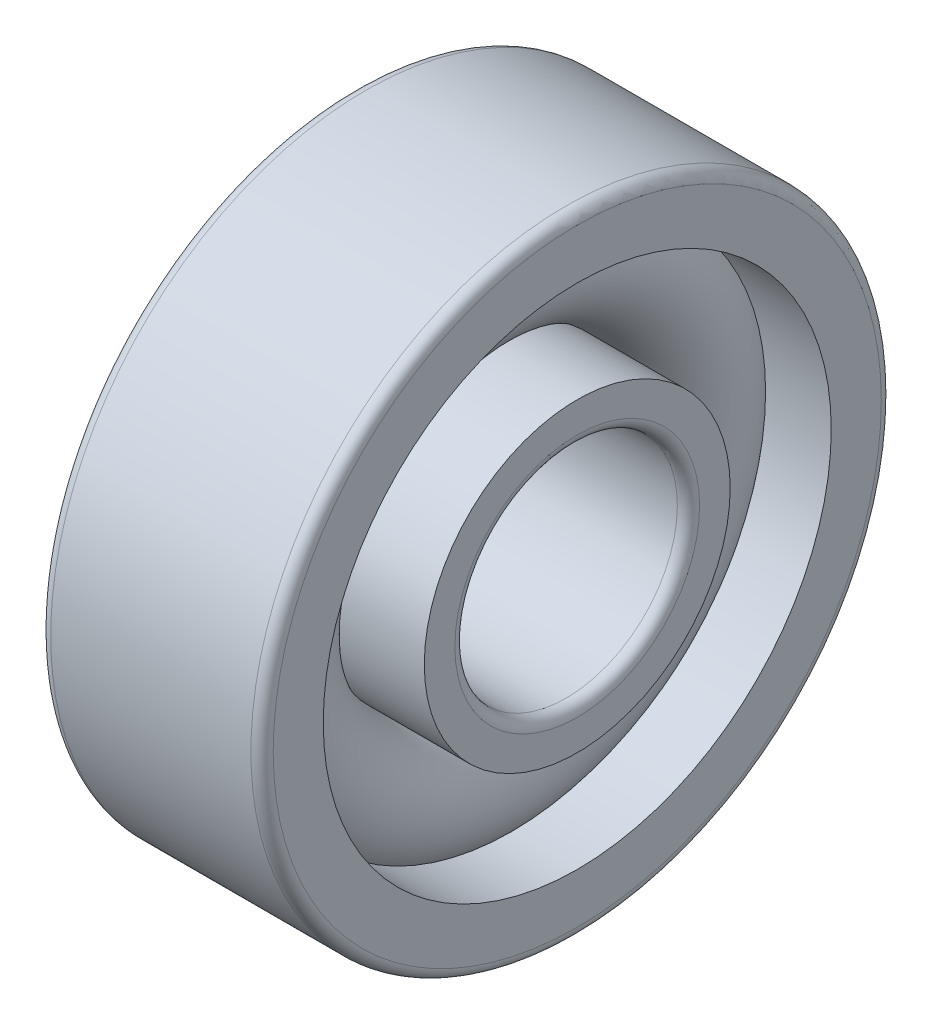
SolidWorks part; units mm, degrees
ref_plane "Plane1" through (0, 0, 0) normal (0, 0, 1) x (1, 0, 0)
ref_plane "Plane2" through (0, 0, 0) normal (0, 1, 0) x (1, 0, 0)
ref_plane "Plane3" through (0, 0, 0) normal (1, 0, 0) x (0, 0, -1)
sketch "Clipboard" plane through (0, 0, 0) normal (0, 0, 1) x (1, 0, 0)
  line L0 (-10, 0) -> (10, 0) construction
  line L1 (0, 0) -> (22.3471, -0.7804)
  line L2 (0, 0) -> (5.7465, 0.2007)
  line L3 (0, 0) -> (22.3471, -0.7804)
  line L4 (0, 0) -> (-22.3573, -0.3902)
  dimension "BallCLRad" = 5.75
sketch "CagSpiSke" plane through (0, 0, 0) normal (0, 0, 1) x (1, 0, 0)
  line L0 (0.4125, 5.475) -> (0.4125, 6.025)
  line L1 (0.4125, 6.025) -> (-0.4125, 6.025)
  line L2 (-0.4125, 6.025) -> (-0.4125, 5.475)
  line L3 (-0.4125, 5.475) -> (0.4125, 5.475)
  line L4 (-20.6375, 0) -> (20.6375, 0) construction
  line L5 (0, 0) -> (0, 23.7692) construction
  dimension "OD" = 12.05
  dimension "ID" = 10.95
revolve "CageSpine" add sketch "CagSpiSke" angle 0.001 about L4
ref_axis "Axis1" through (-50, 0, 0) along (1, 0, 0)
sketch "CagBalSke" plane through (0, 0, 0) normal (0, 0, 1) x (1, 0, 0)
  line L0 (-1.815, 5.75) -> (1.815, 5.75)
  line L1 (-1.905, 5.75) -> (1.905, 5.75) construction
  line L2 (-10, 0) -> (10, 0) construction
  line L3 (0, 0) -> (0, 24) construction
  arc A0 (1.815, 5.75) -> (-1.815, 5.75) centre (0, 5.75) cw
  dimension "BallCLRad" = 5.75
revolve "CageBall" [suppressed] add sketch "CagBalSke" angle 360 about L1 reverse direction yes
pattern_circular "CageBalls" [suppressed] count 2 every 180 about axis through (-50, 0, 0) along (1, 0, 0)
sketch "CagTrmODSke" plane through (0, 0, 0) normal (0, 0, 1) x (1, 0, 0)
  line L0 (1.816, 6.025) -> (1.816, 7.566)
  line L1 (1.816, 7.566) -> (-1.816, 7.566)
  line L2 (-1.816, 7.566) -> (-1.816, 6.025)
  line L3 (-1.816, 6.025) -> (1.816, 6.025)
  line L4 (-20.6375, 0) -> (20.6375, 0) construction
  line L5 (0, 0) -> (0, 25) construction
  dimension "Width" = 3.632
  dimension "ID" = 12.05
  dimension "OD" = 15.132
revolve "CageTrimOD" [suppressed] cut sketch "CagTrmODSke" angle 360 about L4 reverse direction yes
sketch "CagTrmIDSke" plane through (0, 0, 0) normal (0, 0, 1) x (1, 0, 0)
  line L0 (1.816, 3.936) -> (1.816, 5.475)
  line L1 (1.816, 5.475) -> (-1.816, 5.475)
  line L2 (-1.816, 5.475) -> (-1.816, 3.936)
  line L3 (-1.816, 3.936) -> (1.816, 3.936)
  line L4 (-20.6375, 0) -> (20.6375, 0) construction
  line L5 (0, 0) -> (0, 25) construction
  dimension "Width" = 3.632
  dimension "ID" = 7.872
  dimension "OD" = 10.95
revolve "CageTrimID" [suppressed] cut sketch "CagTrmIDSke" angle 360 about L4 reverse direction yes
sketch "BalSimSke" plane through (0, 0, 0) normal (0, 0, 1) x (1, 0, 0)
  line L0 (-10, 0) -> (10, 0) construction
  line L1 (-10, 5.75) -> (10, 5.75) construction
  line L2 (0, 0) -> (0, 23) construction
  circle A0 centre (0, 5.75) radius 1.65
  dimension "BallCLRad" = 5.75
  dimension "Ball_diameter" = 3.3
revolve "BallsSimplified" add sketch "BalSimSke" angle 360 about L0
sketch "BalDetSke" plane through (0, 0, 0) normal (0, 0, 1) x (1, 0, 0)
  line L0 (-1.65, 5.75) -> (1.65, 5.75)
  line L1 (-1.905, 5.75) -> (1.905, 5.75) construction
  line L2 (0, 0) -> (0, 25) construction
  arc A0 (1.65, 5.75) -> (-1.65, 5.75) centre (0, 5.75) cw
  dimension "BallCLRad" = 5.75
  dimension "Ball_diameter" = 3.3
revolve "BallDetailed" [suppressed] add sketch "BalDetSke" angle 360 about L1 reverse direction yes
sketch "InnRacSke" plane through (0, 0, 0) normal (0, 0, 1) x (1, 0, 0)
  line L0 (-1.1961, 4.65) -> (-3, 4.65)
  line L1 (-3, 4.65) -> (-3, 3.3)
  line L2 (-2.7, 3) -> (2.7, 3)
  line L3 (3, 3.3) -> (3, 4.125)
  line L4 (0, 4.125) -> (3, 4.125)
  line L5 (-20.6375, 0) -> (20.6375, 0) construction
  line L6 (0, 0) -> (0, 30) construction
  arc A0 (-3, 3.3) -> (-2.7, 3) centre (-2.7, 3.3) ccw
  arc A1 (2.7, 3) -> (3, 3.3) centre (2.7, 3.3) ccw
  arc A2 (0, 4.125) -> (-1.1961, 4.65) centre (0, 5.75) cw
  dimension "BallCLRad" = 5.75
  dimension "Fillet_radius" = 0.3
  dimension "Ball_diameter" = 3.25
  dimension "ID" = 6
  dimension "OD" = 9.3
  dimension "Width" = 6
revolve "InnerRace" add sketch "InnRacSke" angle 360 about L5 reverse direction yes
sketch "OutRacSke" plane through (0, 0, 0) normal (0, 0, 1) x (1, 0, 0)
  line L0 (0, 7.375) -> (-3, 7.375)
  line L1 (-3, 7.375) -> (-3, 8.2)
  line L2 (-2.7, 8.5) -> (2.7, 8.5)
  line L3 (3, 8.2) -> (3, 6.85)
  line L4 (3, 6.85) -> (1.1961, 6.85)
  line L5 (-20.6375, 0) -> (20.6375, 0) construction
  line L6 (0, 0) -> (0, 30) construction
  arc A0 (-3, 8.2) -> (-2.7, 8.5) centre (-2.7, 8.2) cw
  arc A1 (2.7, 8.5) -> (3, 8.2) centre (2.7, 8.2) cw
  arc A2 (1.1961, 6.85) -> (0, 7.375) centre (0, 5.75) ccw
  dimension "BallCLRad" = 5.75
  dimension "Fillet_radius" = 0.3
  dimension "Ball_diameter" = 3.25
  dimension "Width" = 6
revolve "OuterRace" add sketch "OutRacSke" angle 360 about L5 reverse direction yes
pattern_circular "BallsDetailed" [suppressed] count 2 every 180 about axis through (-50, 0, 0) along (1, 0, 0)
equation "\"BallCLRad@Clipboard\" = ( \"OD@OutRacSke\" + \"ID@InnRacSke\" ) / 4"
equation "\"BallCLRad@BalSimSke\" = \"BallCLRad@Clipboard\""
equation "\"BallCLRad@BalDetSke\" = \"BallCLRad@Clipboard\""
equation "\"BallCLRad@InnRacSke\" = \"BallCLRad@Clipboard\""
equation "\"BallCLRad@OutRacSke\" = \"BallCLRad@Clipboard\""
equation "\"Ball_diameter@InnRacSke\" = \"Ball_diameter@BalDetSke\" - 0.05"
equation "\"Ball_diameter@OutRacSke\" = \"Ball_diameter@BalDetSke\" - 0.05"
equation "\"Ball_diameter@BalSimSke\" = \"Ball_diameter@BalDetSke\""
equation "\"Width@OutRacSke\" = \"Width@InnRacSke\""
equation "\"Fillet_radius@OutRacSke\" = \"Fillet_radius@InnRacSke\""
equation "\"Max_count@Clipboard\" = int( 3.14159265 / atn(( \"Ball_diameter@BalDetSke\" / 2) / sqr( \"BallCLRad@Clipboard\"  *  \"BallCLRad@Clipboard\" - ( \"Ball_diameter@BalDetSke\" / 2) *  ( \"Ball_diameter@BalDetSke\" / 2))))"
equation "\"Max_count@Clipboard\" = ((sgn( \"Max_count@Clipboard\" - \"Count@Clipboard\" )-1)*( \"Max_count@Clipboard\" - \"Count@Clipboard\" ))/-2+ \"Count@Clipboard\""
equation "\"Count@BallsDetailed\" = int( \"Show_count@Clipboard\" ) "
equation "\"Count@BallsDetailed\" = ((sgn( \"Count@BallsDetailed\" - \"Max_count@Clipboard\" )-1)*( \"Count@BallsDetailed\" - \"Max_count@Clipboard\" ))/-2+ \"Max_count@Clipboard\""
equation "\"Count@BallsDetailed\" = ((sgn( \"Count@BallsDetailed\" - \"Min_count@Clipboard\" )+1)*( \"Count@BallsDetailed\" - \"Min_count@Clipboard\"))/2 +\"Min_count@Clipboard\""
equation "\"Angle@BallsDetailed\" = 360.0 / \"Max_count@Clipboard\""
equation "\"BallCLRad@CagBalSke\" = \"BallCLRad@Clipboard\""
equation "\"Count@CageBalls\" = \"Count@BallsDetailed\""
equation "\"Angle@CageBalls\" = \"Angle@BallsDetailed\""
equation "\"Angle@CageSpine\" =  \"Angle@CageBalls\" * ( \"Count@CageBalls\" -1 + int( \"Count@CageBalls\" / \"Max_count@Clipboard\" ) )  + 0.001 -  int( \"Count@CageBalls\" / \"Max_count@Clipboard\" ) * 0.001"
equation "\"Angle@CageSpine\" =  \"Angle@CageSpine\" * int( \"Min_count@Clipboard\" / 2) + int(1 / \"Min_count@Clipboard\")  * 0.001"
equation "\"CageWallOD@CagBalSke\" =  \"Ball_diameter@BalDetSke\" * 1.1"
equation "\"Thickness@CagSpiSke\" =  \"Ball_diameter@BalDetSke\" * 0.25"
equation "\"OD@CagTrmODSke\" = \"BallCLRad@Clipboard\" * 2 + \"CageWallOD@CagBalSke\" + 0.002"
equation "\"ID@CagTrmODSke\" = \"BallCLRad@Clipboard\" * 2 + \"Ball_diameter@BalDetSke\" / 6"
equation "\"OD@CagTrmIDSke\" = \"BallCLRad@Clipboard\" * 2 - \"Ball_diameter@BalDetSke\" / 6"
equation "\"ID@CagTrmIDSke\" = \"BallCLRad@Clipboard\" * 2 - \"CageWallOD@CagBalSke\" + 0.002"
equation "\"OD@CagSpiSke\" = \"ID@CagTrmODSke\""
equation "\"ID@CagSpiSke\" = \"OD@CagTrmIDSke\""
equation "\"Width@CagTrmODSke\" = \"CageWallOD@CagBalSke\" + 0.002"
equation "\"Width@CagTrmIDSke\" = \"CageWallOD@CagBalSke\" + 0.002"
